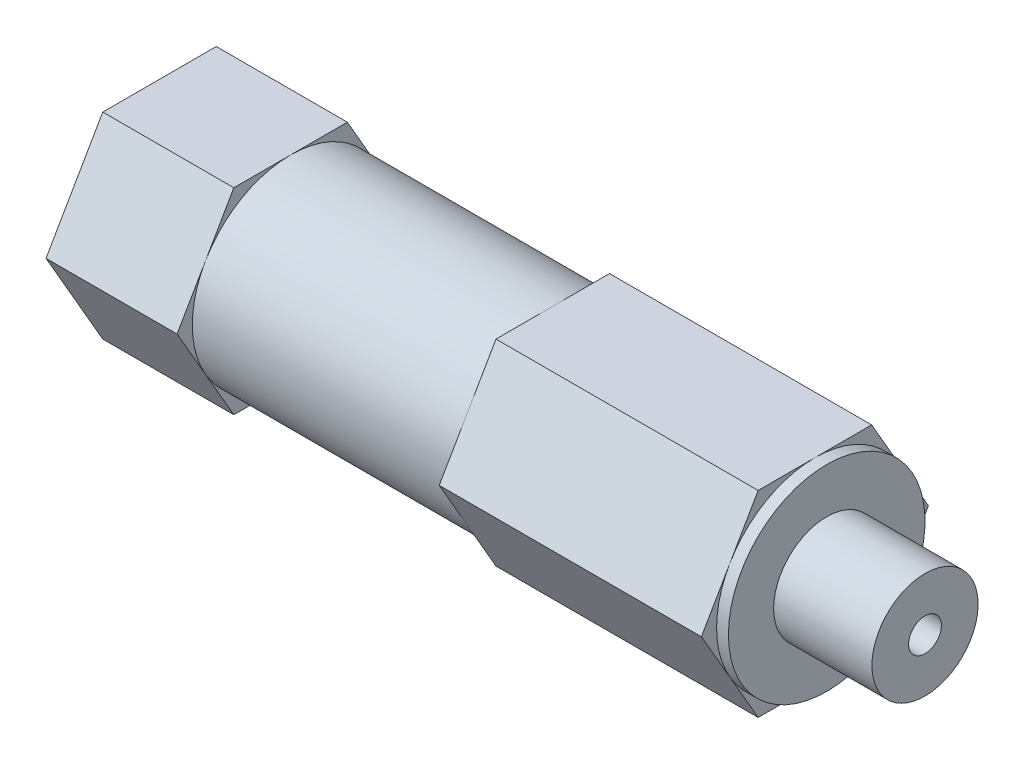
SolidWorks part; units mm, degrees
material "AISI 316 Stainless Steel Sheet (SS)"
ref_plane "Front Plane" through (0, 0, 0) normal (0, 0, 1) x (1, 0, 0)
ref_plane "Top Plane" through (0, 0, 0) normal (0, 1, 0) x (1, 0, 0)
ref_plane "Right Plane" through (0, 0, 0) normal (1, 0, 0) x (0, 0, -1)
sketch "Sketch1" plane through (0, 0, 0) normal (0, 0, 1) x (1, 0, 0)
  line L0 (0, 0) -> (36.4858, 0) construction
  line L1 (0, 9.525) -> (64.643, 9.525)
  line L6 (0, 0) -> (0, 9.525) construction
  line L7 (0, 9.525) -> (0, 4.7625)
  line L8 (0, 4.7625) -> (23.7944, 4.7625)
  line L9 (23.7944, 4.7625) -> (25.3082, 2.413)
  line L10 (25.3082, 2.413) -> (31.9175, 2.413)
  line L11 (31.9175, 2.413) -> (36.7954, 5.5559)
  line L12 (36.7954, 5.5559) -> (36.7954, 7.5369)
  line L13 (36.7954, 7.5369) -> (40.4579, 7.5369)
  line L14 (40.4579, 7.5369) -> (40.4579, 4.5892)
  line L15 (40.4579, 4.5892) -> (59.7788, 4.5892)
  line L16 (59.7788, 4.5892) -> (59.7788, 1.5875)
  line L17 (59.7788, 1.5875) -> (74.168, 1.5875)
  line L18 (74.168, 1.5875) -> (74.168, 5.1435)
  line L19 (74.168, 5.1435) -> (64.643, 5.1435)
  line L20 (64.643, 5.1435) -> (64.643, 9.525)
  dimension "D1" = 74.168
  dimension "D2" = 19.05
  dimension "D3" = 10.287
  dimension "D4" = 9.525
  dimension "D5" = 4.826
  dimension "D6" = 3.175
  dimension "D7" = 9.525
revolve "Revolve1" add sketch "Sketch1" angle 360 about L0
sketch "Sketch8" plane through (0, 0, 0) normal (-1, 0, 0) x (0, 0, 1)
  line L0 (0, 0) -> (10.9985, 0) construction
  line L1 (-10.9985, 0) -> (-5.4993, -9.525)
  line L2 (-5.4993, -9.525) -> (5.4993, -9.525)
  line L3 (5.4993, -9.525) -> (10.9985, 0)
  line L4 (10.9985, 0) -> (5.4993, 9.525)
  line L5 (5.4993, 9.525) -> (-5.4993, 9.525)
  line L6 (-5.4993, 9.525) -> (-10.9985, 0)
  circle A0 centre (0, 0) radius 9.525 construction
  circle A1 centre (0, 0) radius 9.525
  circle A2 centre (0, 0) radius 9.525 construction
  circle M10 centre (0, 0) radius 9.525
extrude "Boss-Extrude1" add sketch "Sketch8" against normal blind 12.7 contours L4 L5 M10 | L5 L6 M10 | L6 L1 M10 | L1 L2 M10 | L2 L3 M10 | L3 L4 M10 region at (0, 0, -9.8447) region at (0, -8.5257, -4.9223) region at (0, 8.5257, -4.9223) region at (0, -8.5257, 4.9223) region at (0, 8.5257, 4.9223) region at (0, 0, 9.8447)
extrude "Boss-Extrude2" add sketch "Sketch8<3>" against normal blind 25.4 from offset 38.1 contours L4 L5 M10 | L5 L6 M10 | L6 L1 M10 | L1 L2 M10 | L2 L3 M10 | L3 L4 M10 region at (0, 0, -9.8447) region at (0, -8.5257, -4.9223) region at (0, 8.5257, -4.9223) region at (0, -8.5257, 4.9223) region at (0, 8.5257, 4.9223) region at (0, 0, 9.8447) offset against normal yes
sketch "Sketch8<3>" plane through (0, 0, 0) normal (-1, 0, 0) x (0, 0, 1) same geometry as "Sketch8"
